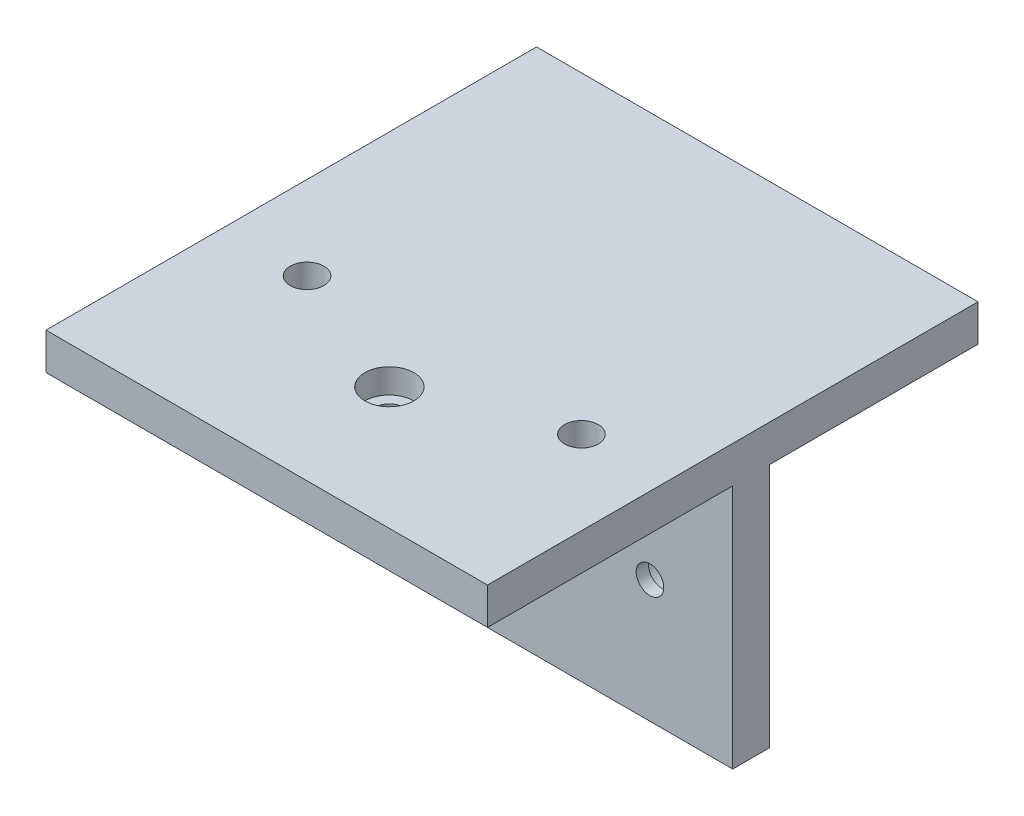
SolidWorks part; units mm, degrees
ref_plane "Front Plane" through (0, 0, 0) normal (0, 0, 1) x (1, 0, 0)
ref_plane "Top Plane" through (0, 0, 0) normal (0, 1, 0) x (1, 0, 0)
ref_plane "Right Plane" through (0, 0, 0) normal (1, 0, 0) x (0, 0, -1)
sketch "Sketch1" plane through (0, 0, 0) normal (1, 0, 0) x (0, 0, -1)
  line L0 (-20, 20) -> (20, 20)
  line L1 (-20, 20) -> (20, 20) construction
  line L2 (-20, 20) -> (-20, -20) construction
  line L3 (-20, -20) -> (20, -20) construction
  line L4 (20, 20) -> (20, -20) construction
  line L5 (-20, 20) -> (20, -20) construction
  line L6 (-20, -20) -> (20, 20) construction
  line L7 (20, 20) -> (20, -20)
  line L8 (26, 20) -> (60, 20)
  line L10 (-20, 20) -> (-20, 26)
  line L11 (-20, 26) -> (60, 26)
  line L12 (60, 26) -> (60, 20)
  line L13 (20, -20) -> (26, -20)
  line L14 (26, -20) -> (26, 20)
  point P0 (0, 0)
  dimension "D1" = 40
  dimension "D2" = 40
  dimension "D3" = 6
  dimension "D4" = 6
extrude "Boss-Extrude1" add sketch "Sketch1" along normal mid plane 72 contours L12 L11 L10 L0 L8 region at (0, 15.3333, -21)
sketch "Sketch2" plane through (0, 0, -26) normal (0, 0, -1) x (-1, 0, 0)
  line L0 (-22.5, 20) -> (-22.5, -20) construction
  line L1 (-36, 20) -> (36, 20) construction
  line L2 (-36, -20) -> (36, -20) construction
  line L3 (22.5, 20) -> (22.5, -20) construction
  line L4 (-36, 20) -> (36, 20) construction
  line L6 (22.5, -20) -> (-22.5, -20) construction
  circle A0 centre (-22.5, 0) radius 2.25
  circle A1 centre (22.5, 0) radius 2.25
  point P10 (0, -20)
  dimension "D2" = 4.5
  dimension "D1" = 45
extrude "Cut-Extrude1" cut sketch "Sketch2" against normal up to next
sketch "Sketch3" plane through (0, 20, 0) normal (0, -1, 0) x (1, 0, 0)
  circle A0 centre (0, 0) radius 2.25
  dimension "D2" = 4.5
extrude "Cut-Extrude2" cut sketch "Sketch3" against normal up to next
sketch "Sketch4" plane through (0, 0, -26) normal (0, 0, -1) x (-1, 0, 0)
  circle A0 centre (-22.5, 0) radius 4
  circle A1 centre (22.5, 0) radius 4
  dimension "D1" = 8
extrude "Cut-Extrude3" cut sketch "Sketch4" against normal blind 4
sketch "Sketch5" plane through (0, 26, 0) normal (0, 1, 0) x (1, 0, 0)
  circle A1 centre (0, 0) radius 4
  dimension "D1" = 8
extrude "Cut-Extrude4" cut sketch "Sketch5" against normal blind 4
sketch "Sketch7" plane through (0, 26, 0) normal (0, 1, 0) x (1, 0, 0)
  line L0 (-22.375, 8.95) -> (22.375, 8.95) construction
  circle A0 centre (-22.375, 8.95) radius 2.25
  circle A1 centre (22.375, 8.95) radius 2.25
  point P2 (0, 8.95)
  dimension "D3" = 4.5
  dimension "D1" = 44.75
  dimension "D2" = 8.95
extrude "Cut-Extrude5" cut sketch "Sketch7" against normal up to next
sketch "Sketch8" plane through (0, 26, 0) normal (0, 1, 0) x (1, 0, 0)
  circle A0 centre (-22.375, 8.95) radius 2.75
  circle A1 centre (22.375, 8.95) radius 2.75
  dimension "D1" = 5.5
extrude "Cut-Extrude6" cut sketch "Sketch8" against normal blind 4
equation "\"ClearHole\"=4.5"
equation "\"D2@Sketch2\"=\"ClearHole\""
equation "\"D2@Sketch3\"=\"ClearHole\""
equation "\"SocketClear\"=8"
equation "\"D1@Sketch4\"=\"SocketClear\""
equation "\"SocketDepth\"=4"
equation "\"D1@Cut-Extrude3\"=\"SocketDepth\""
equation "\"D4@Sketch1\"=\"D3@Sketch1\""
equation "\"Thicknes\"=6"
equation "\"D3@Sketch1\"=\"Thicknes\""
equation "\"D1@Sketch5\"=\"SocketClear\""
equation "\"D3@Sketch7\"=\"ClearHole\""
equation "\"MFourInsert\"=5.5"
equation "\"D1@Sketch8\"=\"MFourInsert\""
